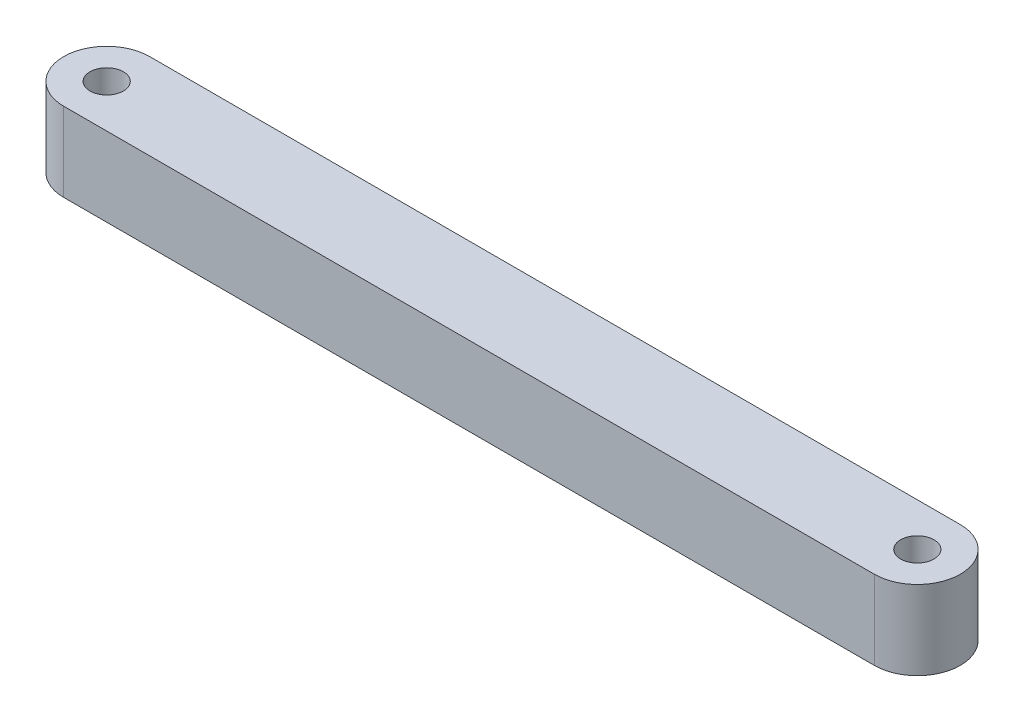
SolidWorks part; units mm, degrees
ref_plane "Front Plane" through (0, 0, 0) normal (0, 0, 1) x (1, 0, 0)
ref_plane "Top Plane" through (0, 0, 0) normal (0, 1, 0) x (1, 0, 0)
ref_plane "Right Plane" through (0, 0, 0) normal (1, 0, 0) x (0, 0, -1)
sketch "Sketch1" plane through (0, 0, 0) normal (0, 1, 0) x (1, 0, 0)
  line L0 (0, 0) -> (104.775, 0) construction
  line L1 (0, 5.5563) -> (104.775, 5.5563)
  line L2 (0, -5.5563) -> (104.775, -5.5563)
  arc A1 (0, 5.5563) -> (0, -5.5563) centre (0, 0) ccw
  arc A2 (104.775, -5.5563) -> (104.775, 5.5563) centre (104.775, 0) ccw
  point P3 (52.3875, 0)
  dimension "D1" = 11.1125
  dimension "D2" = 104.775
extrude "Boss-Extrude1" add sketch "Sketch1" along normal blind 10.2108
sketch "Sketch2" plane through (0, 10.2108, 0) normal (0, 1, 0) x (1, 0, 0)
  circle A1 centre (104.775, 0) radius 2.159
  circle A2 centre (0, 0) radius 2.159
  dimension "D3" = 4.318
  dimension "D1" = 104.775
extrude "Cut-Extrude1" cut sketch "Sketch2" against normal through all
ref_plane "Plane1" through (0, 5.1054, 0) normal (0, 1, 0) x (1, 0, 0)
